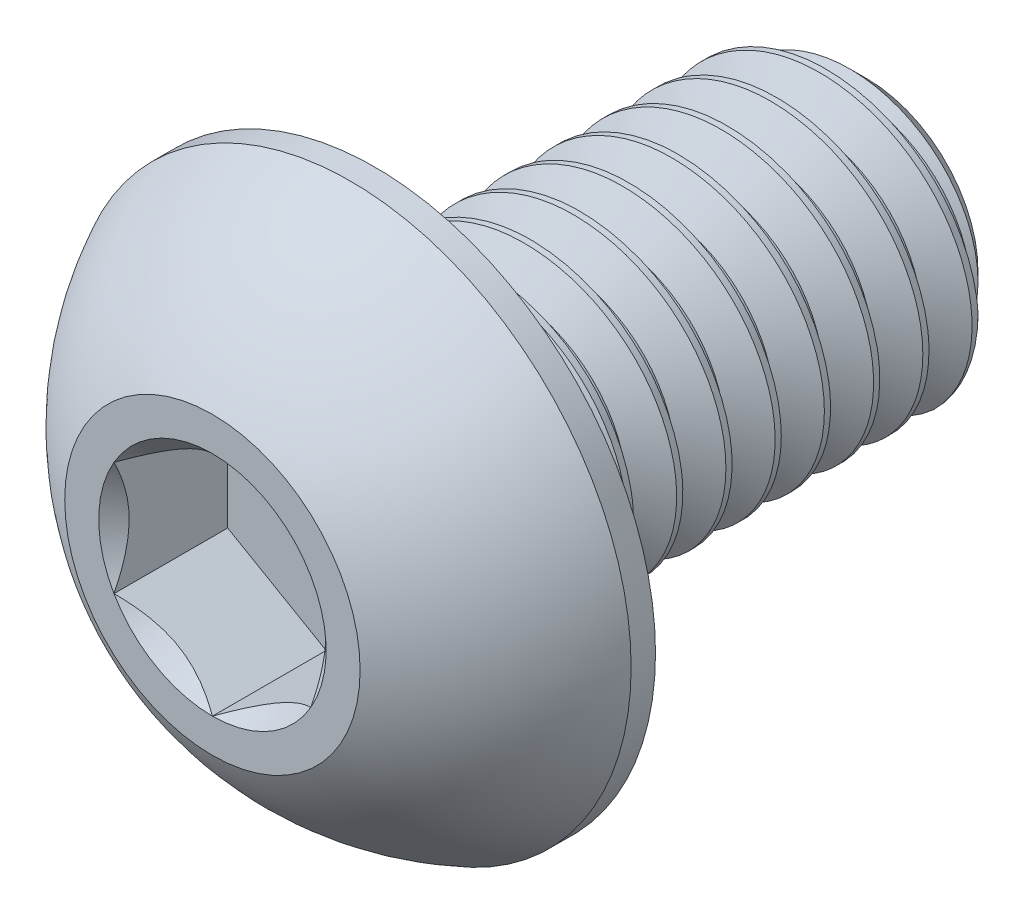
SolidWorks part; units mm, degrees
ref_plane "Front" through (0, 0, 0) normal (0, 0, 1) x (1, 0, 0)
ref_plane "Top" through (0, 0, 0) normal (0, 1, 0) x (1, 0, 0)
ref_plane "Right" through (0, 0, 0) normal (1, 0, 0) x (0, 0, -1)
sketch "Sketch1" plane through (0, 0, 0) normal (1, 0, 0) x (0, 0, -1)
  line L2 (1.65, 1.5) -> (6.65, 1.5)
  line L3 (6.65, 1.5) -> (6.65, 0)
  line L4 (6.65, 0) -> (1.65, 0)
  line L6 (1.4025, 2.85) -> (1.65, 2.85) construction
  line L7 (6.65, 1.5) -> (6.65, -1.5) construction
  line L8 (0, 0) -> (1.65, 0) construction
  line L9 (1.65, 2.85) -> (1.65, -2.85) construction
  line L11 (1.65, 1.5) -> (1.65, 0)
  line L13 (0, 1) -> (0, -1) construction
  line L14 (0, 1) -> (0, 1.5) construction
  arc A3 (0, 1.5) -> (1.4025, 2.85) centre (2.7948, 0) cw construction
  dimension "D1" = 0.2475
revolve "Revolve1" add sketch "Sketch1" angle 360 mid plane about L4
sketch "Sketch3" plane through (0, 0, -6.65) normal (0, 0, -1) x (-1, 0, 0)
  circle A0 centre (0, 0) radius 1.5
curve "Helix/Spiral1" pitch 0.5 height 5.5 radius 1.5 centre (0, 0, -6.65) axis (0, 0, 1) start towards (0, 1, 0)
sketch "Sketch2" plane through (0, 0, 0) normal (1, 0, 0) x (0, 0, -1)
  line L0 (6.65, 1.5) -> (7.0875, 1.5)
  line L1 (7.0875, 1.5) -> (6.9, 1.1752)
  line L2 (6.9, 1.1752) -> (6.8375, 1.1752)
  line L3 (6.8375, 1.1752) -> (6.65, 1.5)
  line L4 (6.7437, 1.3376) -> (6.9937, 1.3376) construction
  dimension "D1" = 60
  dimension "D2" = 0.0625
  dimension "D3" = 0.25
chamfer "Chamfer1" distance 0.375 angle 45 1 edges at (0, 1.5, -6.65)
sweep "Cut-Sweep1" cut profiles "Sketch2" path "Helix/Spiral1" align with end faces yes
sketch "Sketch7" plane through (0, 0, 0) normal (1, 0, 0) x (0, 0, -1)
  line L6 (1.4025, 2.85) -> (1.65, 2.85) construction
  line L8 (0, 0) -> (1.65, 0) construction
  line L11 (1.65, 2.85) -> (1.65, -2.85) construction
  line L12 (1.4025, 2.85) -> (1.65, 2.85)
  line L13 (0, 0) -> (1.65, 0)
  line L14 (0, 1) -> (0, -1) construction
  line L15 (1.65, 2.85) -> (1.65, 0)
  line L16 (0, 1.5) -> (0, 0)
  arc A2 (1.4025, 2.85) -> (0, 1.5) centre (2.7948, 0) ccw construction
  arc A3 (1.4025, 2.85) -> (0, 1.5) centre (2.7948, 0) ccw
revolve "Revolve2" add sketch "Sketch7" angle 360 mid plane about L13
sketch "Sketch5" plane through (0, 0, 0) normal (0, 0, 1) x (1, 0, 0)
  line L1 (1, -0.5774) -> (1, 0.5774)
  line L2 (1, 0.5774) -> (0, 1.1547)
  line L3 (0, 1.1547) -> (-1, 0.5774)
  line L4 (-1, 0.5774) -> (-1, -0.5774)
  line L5 (-1, -0.5774) -> (0, -1.1547)
  line L6 (0, -1.1547) -> (1, -0.5774)
  circle A0 centre (0, 0) radius 1 construction
extrude "Cut-Extrude2" cut sketch "Sketch5" against normal blind 1.155
sketch "Sketch6" plane through (0, 0, 0) normal (0, 0, 1) x (1, 0, 0)
  circle A0 centre (0, 0) radius 1.1547
extrude "Cut-Extrude3" cut sketch "Sketch6" against normal blind 1.155 draft 45
sketch "Sketch9" [suppressed] plane through (0, 0, -5.0546) normal (0, 0, 1) x (1, 0, 0)
  circle A2 centre (0, 0) radius 4.7625
extrude "Boss-Extrude2" [suppressed] add sketch "Sketch9" against normal offset from surface (6.35 mm away) 31.75 up to face at (0, 1.125, -6.65)
sketch "Sketch10" plane through (0, 0, 0) normal (1, 0, 0) x (0, 0, -1)
  line L0 (6.65, 1.5) -> (6.65, -1.5) construction
  point P0 (5.9, -1.5)
  dimension "D1" = 0.75
equation "\"D3@Helix/Spiral1\" = \"Lg@Sketch1\" + \"D4@Helix/Spiral1\""
equation "\"D2@Sketch2\" = \"D4@Helix/Spiral1\" * .125"
equation "\"D3@Sketch2\" = \"D4@Helix/Spiral1\" * .5"
equation "\"D1@Chamfer1\" = \"D4@Helix/Spiral1\" * .75"
equation "\"D1@Cut-Extrude2\" = \"Head Ht@Sketch1\" * .7"
equation "\"D1@Sketch1\" = \"Head Ht@Sketch1\" * .15"
equation "\"D1@Sketch10\" = \"D4@Helix/Spiral1\" * 1.5"
equation "\"D1@Cut-Extrude3\" = \"D1@Cut-Extrude2\""
